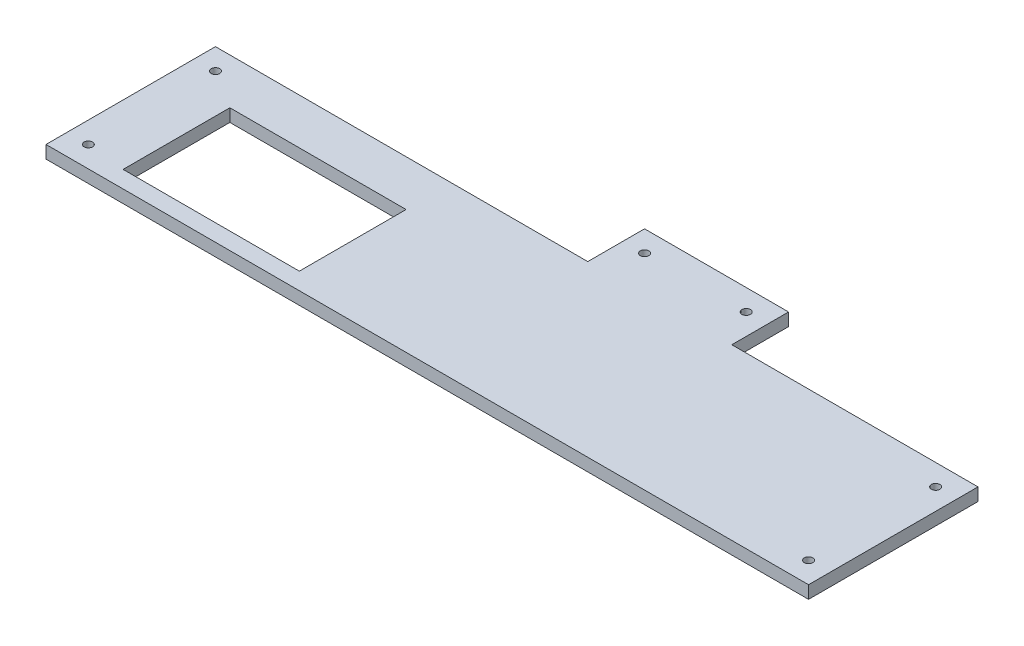
SolidWorks part; units mm, degrees
ref_plane "Front Plane" through (0, 0, 0) normal (0, 0, 1) x (1, 0, 0)
ref_plane "Top Plane" through (0, 0, 0) normal (0, 1, 0) x (1, 0, 0)
ref_plane "Right Plane" through (0, 0, 0) normal (1, 0, 0) x (0, 0, -1)
sketch "Sketch1" plane through (0, 0, 0) normal (0, 1, 0) x (1, 0, 0)
  line L8 (450, 100) -> (-450, 100)
  line L9 (-450, 100) -> (-450, -100)
  line L10 (-450, -100) -> (450, -100)
  line L11 (450, -100) -> (450, 100)
  circle A4 centre (425, -75) radius 5
  circle A5 centre (425, 75) radius 5
  circle A6 centre (-425, -75) radius 5
  circle A7 centre (-425, 75) radius 5
extrude "Boss-Extrude1" add sketch "Sketch1" against normal blind 15
sketch "Sketch2" plane through (0, -15, 0) normal (0, -1, 0) x (1, 0, 0)
  line L1 (-379, 80) -> (-171, 80)
  line L2 (-379, 80) -> (-379, -46)
  line L3 (-379, -46) -> (-171, -46)
  line L4 (-171, 80) -> (-171, -46)
  point P4 (0, 0)
extrude "Shredder Opening" cut sketch "Sketch2" against normal through all
sketch "Sketch3" plane through (0, 0, 0) normal (0, 1, 0) x (1, 0, 0)
  line L0 (450, 100) -> (-450, 100) construction
  line L1 (159.4257, 100) -> (-10.5743, 100)
  line L2 (159.4257, 100) -> (159.4257, 167)
  line L3 (159.4257, 167) -> (-10.5743, 167)
  line L4 (-10.5743, 100) -> (-10.5743, 167)
  line L5 (139.4257, -91) -> (139.4257, 147) construction
  line L6 (9.4257, 147) -> (139.4257, 147) construction
  line L7 (9.4257, -91) -> (9.4257, 147) construction
  line L8 (74.4257, 167) -> (74.4257, 267.7218) construction
  circle A0 centre (134.4257, 142) radius 5 construction
  circle A1 centre (134.4257, 142) radius 5
  circle A2 centre (14.4257, 142) radius 5
  dimension "D1" = 20
  dimension "D2" = 20
  dimension "D3" = 20
extrude "Legs add on" add sketch "Sketch3" against normal through all
